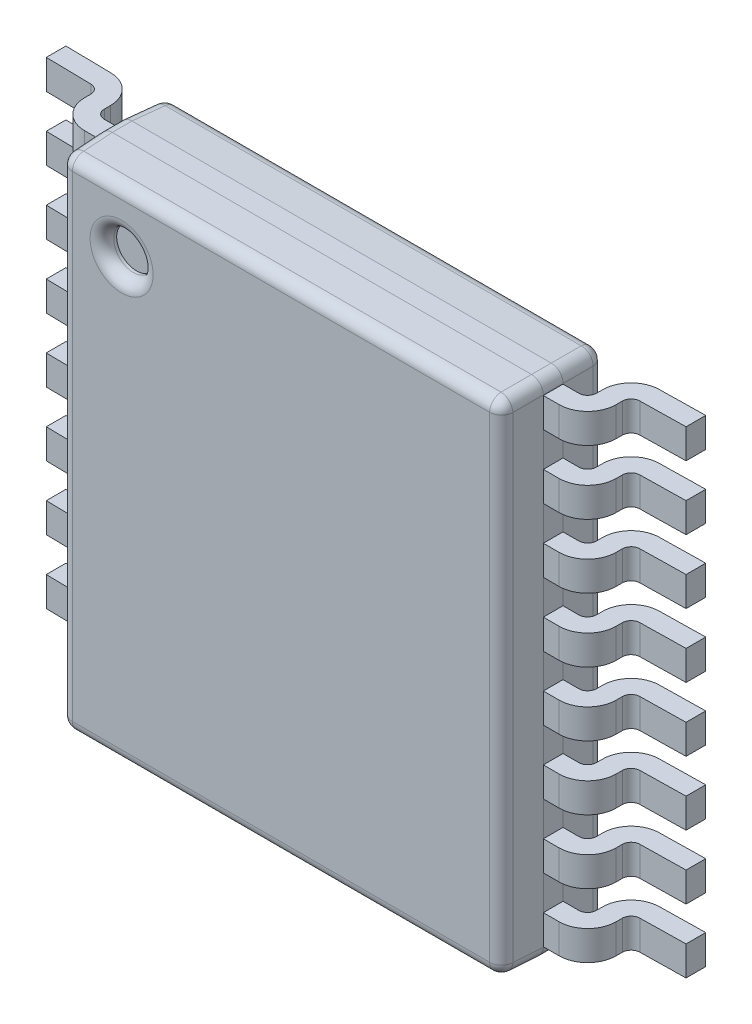
SolidWorks part; units mm, degrees
ref_plane "Front Plane" through (0, 0, 0) normal (0, 0, 1) x (1, 0, 0)
ref_plane "Top Plane" through (0, 0, 0) normal (0, 1, 0) x (1, 0, 0)
ref_plane "Right Plane" through (0, 0, 0) normal (1, 0, 0) x (0, 0, -1)
sketch "Sketch1" plane through (0, 0, 0) normal (0, 0, 1) x (1, 0, 0)
  line L1 (-2.25, 2.55) -> (2.25, 2.55)
  line L2 (-2.25, 2.55) -> (-2.25, -2.55)
  line L3 (-2.25, -2.55) -> (2.25, -2.55)
  line L4 (2.25, 2.55) -> (2.25, -2.55)
  dimension "D1" = 2.25
  dimension "D2" = 4.5
  dimension "D3" = 2.55
  dimension "D4" = 5.1
extrude "Boss-Extrude1" add sketch "Sketch1" along normal blind 1.05 from offset 0.01
ref_plane "Plane1" through (0, 2.275, 0) normal (0, 1, 0) x (-1, 0, 0)
sketch "Sketch2" plane through (0, 2.275, 0) normal (0, 1, 0) x (-1, 0, 0)
  line L0 (-2.41, 0.645) -> (-2.25, 0.645)
  line L1 (-2.25, 1.06) -> (-2.25, 0.01) construction
  line L2 (-2.7, 0.355) -> (-2.7, 0.293)
  line L3 (-2.7884, 0.2031) -> (-3.25, 0.195)
  line L4 (-3.25, 0.195) -> (-3.25, -0.005)
  line L5 (-3.25, -0.005) -> (-2.7849, 0.0031)
  line L6 (-2.5, 0.2931) -> (-2.5, 0.355)
  line L7 (-2.41, 0.445) -> (-2.25, 0.445)
  line L8 (-2.25, 0.645) -> (-2.25, 0.445)
  line L9 (2.25, 0.535) -> (-2.25, 0.535) construction
  line L10 (2.25, 1.06) -> (2.25, 0.01) construction
  arc A0 (-2.41, 0.445) -> (-2.5, 0.355) centre (-2.41, 0.355) ccw
  arc A1 (-2.7884, 0.2031) -> (-2.7, 0.293) centre (-2.79, 0.293) ccw
  arc A2 (-2.7, 0.355) -> (-2.41, 0.645) centre (-2.41, 0.355) cw
  arc A3 (-2.7849, 0.0031) -> (-2.5, 0.2931) centre (-2.79, 0.2931) ccw
  point P16 (-2.5, 0.445)
  point P22 (-2.7, 0.645)
  dimension "D9" = 0.09
  dimension "D10" = 0.09
  dimension "D11" = 0.29
  dimension "D12" = 0.29
  dimension "D1" = 0.11
  dimension "D2" = 0.2
  dimension "D3" = 1
  dimension "D4" = 0.2
  dimension "D5" = 0.25
  dimension "D6" = 0.54
  dimension "D7" = 89
  dimension "D8" = 0.2
extrude "Boss-Extrude2" add sketch "Sketch2" along normal mid plane 0.3
pattern_linear "LPattern1" count 8 spacing 0.65 along (0, -1, 0) of "Boss-Extrude2"
mirror "Mirror1" about plane through (0, 0, 0) normal (1, 0, 0) of "LPattern1", "Boss-Extrude2"
chamfer "Chamfer5" distance 0.415 angle 2 4 edges at (-2.25, 0, 1.06) (2.25, 0, 1.06) (0, -2.55, 1.06) (0, 2.55, 1.06)
chamfer "Chamfer6" distance 0.435 angle 3 4 edges at (2.25, 0, 0.01) (-2.25, 0, 0.01) (0, -2.55, 0.01) (0, 2.55, 0.01)
fillet "Fillet3" radius 0.12 20 edges at (-2.2355, 0, 1.06) (2.2272, 0, 0.01) (-2.2272, 0, 0.01) (-2.2428, 2.5428, 0.8525) (-2.25, 2.55, 0.545) (-2.2386, 2.5386, 0.2275) (0, 2.5272, 0.01) (2.2386, 2.5386, 0.2275) (2.25, 2.55, 0.545) (2.2428, 2.5428, 0.8525) (2.2428, -2.5428, 0.8525) (2.25, -2.55, 0.545) (2.2386, -2.5386, 0.2275) (0, -2.5272, 0.01) (-2.2386, -2.5386, 0.2275) (-2.25, -2.55, 0.545) (-2.2428, -2.5428, 0.8525) (0, 2.5355, 1.06) (2.2355, 0, 1.06) (0, -2.5355, 1.06)
sketch "Sketch5" plane through (0, 0, 1.06) normal (0, 0, 1) x (1, 0, 0)
  circle A0 centre (-1.6196, 1.9196) radius 0.2
  dimension "D3" = 0.4
  dimension "D1" = 0.5
  dimension "D2" = 0.5
extrude "Cut-Extrude1" cut sketch "Sketch5" against normal blind 0.15
fillet "Fillet4" radius 0.12 1 edges at (-1.4196, 1.9196, 1.06)
